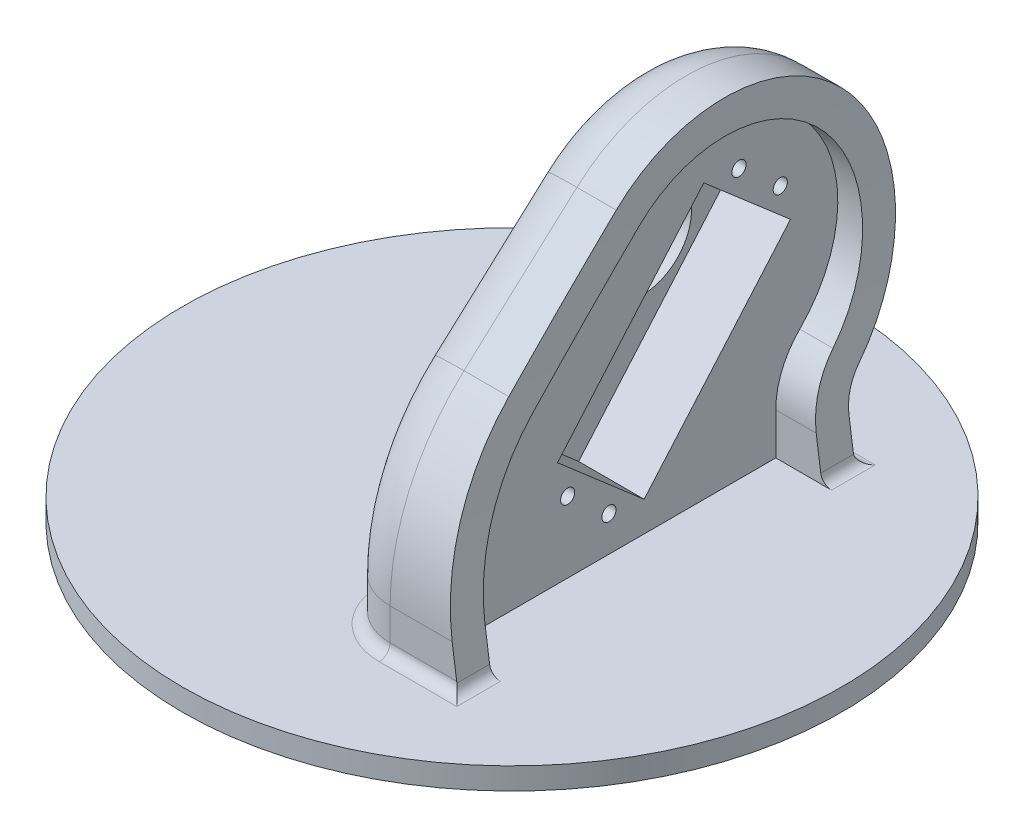
SolidWorks part; units mm, degrees
ref_plane "Front Plane" through (0, 0, 0) normal (0, 0, 1) x (1, 0, 0)
ref_plane "Top Plane" through (0, 0, 0) normal (0, 1, 0) x (1, 0, 0)
ref_plane "Right Plane" through (0, 0, 0) normal (1, 0, 0) x (0, 0, -1)
sketch "Sketch1" plane through (0, 0, 0) normal (0, 1, 0) x (1, 0, 0)
  circle A0 centre (0, 0) radius 60.3947
  dimension "D1" = 120.7894
extrude "Boss-Extrude1" add sketch "Sketch1" along normal blind 1
sketch "Sketch3" plane through (0, 0, 0) normal (1, 0, 0) x (0, 0, -1)
  line L0 (-30.34, 1) -> (30.34, 1)
  line L1 (60.3947, 1) -> (-60.3947, 1) construction
  line L2 (30.34, 1) -> (30.34, 8.64)
  line L3 (-30.34, 1) -> (-30.34, 8.86)
  line L4 (1.924, 53.717) -> (-18.7678, 34.9648)
  arc A0 (30.34, 8.64) -> (34.7349, 19.2481) centre (45.34, 8.64) cw
  arc A1 (34.7349, 19.2481) -> (1.924, 53.717) centre (17.9072, 36.0806) ccw
  arc A2 (-30.34, 8.86) -> (-18.7678, 34.9648) centre (4.89, 8.86) cw
  circle A3 centre (17.9072, 36.0806) radius 9
  point P5 (0, 1)
  point P11 (0, 0)
  point P14 (0, 0)
  dimension "D3" = 15
  dimension "D5" = 35.23
  dimension "D6" = 18
  dimension "D1" = 60.68
  dimension "D2" = 7.64
  dimension "D4" = 7.86
  dimension "D7" = 40.28
extrude "Boss-Extrude3" add sketch "Sketch3" along normal blind 14 from offset 4
sketch "Sketch4" plane through (0, 0, 0) normal (1, 0, 0) x (0, 0, -1)
  line L0 (17.1497, 51.2561) -> (33.0333, 37.5189)
  line L1 (17.1497, 51.2561) -> (-9.6705, 20.2452)
  line L2 (33.0333, 37.5189) -> (6.2131, 6.508)
  line L3 (-9.6705, 20.2452) -> (6.2131, 6.508)
  line L4 (60.3947, 1) -> (-60.3947, 1) construction
  line L5 (3.7396, 35.7507) -> (19.6232, 22.0135) construction
  line L6 (19.6232, 22.0135) -> (3.7396, 35.7507) construction
  line L7 (3.7396, 35.7507) -> (3.5328, 35.6133) construction
  line L8 (11.6814, 28.8821) -> (27.3811, 47.0348) construction
  line L9 (27.3811, 47.0348) -> (11.6814, 28.8821) construction
  line L10 (23.5993, 50.3055) -> (31.1629, 43.764) construction
  circle A0 centre (17.9072, 36.0806) radius 9 construction
  circle A1 centre (23.5993, 50.3055) radius 1.3
  circle A2 centre (31.1629, 43.764) radius 1.3
  circle A3 centre (-0.2364, 7.4586) radius 1.3
  circle A4 centre (-7.8, 14.0001) radius 1.3
  point P16 (27.3811, 47.0348)
  dimension "D7" = 2.6
  dimension "D8" = 2.6
  dimension "D1" = 41
  dimension "D2" = 21
  dimension "D3" = 10.5
  dimension "D4" = 49.145
  dimension "D5" = 10
  dimension "D6" = 3.5
extrude "Cut-Extrude1" cut sketch "Sketch4" along normal through all from offset 6
sketch "Sketch8" plane through (18, 0, 0) normal (1, 0, 0) x (0, 0, -1)
  line L0 (-30.34, 1) -> (30.34, 1) construction
  line L1 (-30.34, 1) -> (30.34, 1)
  line L15 (-33.34, 8.86) -> (-33.34, 1)
  line L16 (33.34, 1) -> (33.34, 8.64)
  line L17 (-0.0906, 55.94) -> (-20.7824, 37.1878)
  line L18 (-33.34, 8.86) -> (-33.34, 1) construction
  line L19 (33.34, 1) -> (33.34, 8.64) construction
  line L20 (-0.0906, 55.94) -> (-20.7824, 37.1878) construction
  line L31 (36.34, 1) -> (36.34, 8.64)
  line L32 (-2.1051, 58.1629) -> (-22.797, 39.4107)
  line L33 (-36.34, 8.86) -> (-36.34, 1)
  line L34 (33.34, 1) -> (33.34, 8.64)
  line L35 (-0.0906, 55.94) -> (-20.7824, 37.1878)
  line L36 (-33.34, 8.86) -> (-33.34, 1)
  line L37 (33.34, 1) -> (33.34, 8.64) construction
  line L38 (-0.0906, 55.94) -> (-20.7824, 37.1878) construction
  line L39 (-33.34, 8.86) -> (-33.34, 1) construction
  line L40 (-36.34, 1) -> (-27.34, 1)
  line L41 (30.34, 1) -> (36.34, 1)
  arc A14 (-20.7824, 37.1878) -> (-33.34, 8.86) centre (4.89, 8.86) ccw
  arc A15 (36.8559, 17.1265) -> (33.34, 8.64) centre (45.34, 8.64) ccw
  arc A16 (36.8559, 17.1265) -> (-0.0906, 55.94) centre (17.9072, 36.0806) ccw
  arc A17 (-20.7824, 37.1878) -> (-33.34, 8.86) centre (4.89, 8.86) ccw construction
  arc A18 (36.8559, 17.1265) -> (33.34, 8.64) centre (45.34, 8.64) ccw construction
  arc A19 (36.8559, 17.1265) -> (-0.0906, 55.94) centre (17.9072, 36.0806) ccw construction
  arc A28 (38.9769, 15.0049) -> (36.34, 8.64) centre (45.34, 8.64) ccw
  arc A29 (38.9769, 15.0049) -> (-2.1051, 58.1629) centre (17.9072, 36.0806) ccw
  arc A30 (-22.797, 39.4107) -> (-36.34, 8.86) centre (4.89, 8.86) ccw
  arc A31 (36.8559, 17.1265) -> (33.34, 8.64) centre (45.34, 8.64) ccw
  arc A32 (36.8559, 17.1265) -> (-0.0906, 55.94) centre (17.9072, 36.0806) ccw
  arc A33 (-20.7824, 37.1878) -> (-33.34, 8.86) centre (4.89, 8.86) ccw
  arc A34 (36.8559, 17.1265) -> (33.34, 8.64) centre (45.34, 8.64) ccw construction
  arc A35 (36.8559, 17.1265) -> (-0.0906, 55.94) centre (17.9072, 36.0806) ccw construction
  arc A36 (-20.7824, 37.1878) -> (-33.34, 8.86) centre (4.89, 8.86) ccw construction
  arc A37 (1.924, 53.717) -> (-27.34, 1) centre (70.6562, -18.9182) ccw
  line M1 (30.34, 1) -> (30.34, 8.64)
  arc M2 (30.34, 8.64) -> (34.7349, 19.2481) centre (45.34, 8.64) cw
  arc M3 (34.7349, 19.2481) -> (1.924, 53.717) centre (17.9072, 36.0806) ccw
  line M4 (1.924, 53.717) -> (-18.7678, 34.9648)
  arc M5 (-18.7678, 34.9648) -> (-30.34, 8.86) centre (4.89, 8.86) ccw
  line M6 (-30.34, 8.86) -> (-30.34, 1)
  dimension "D5" = 100
  dimension "D4" = 3
  dimension "D1" = 3
  dimension "D2" = 3
  dimension "D3" = 3
extrude "Boss-Extrude4" add sketch "Sketch8" along normal blind 9 and the other way up to surface (14 mm away) contours L32 A30 L33 L40 L41 L31 A28 A29 M6 M5 M4 M3 M2 M1 region at (18, 1.996, 31.84) region at (18, 2.0618, 34.84) other way up to face at (4, 20.7286, -4.4128)
sketch "Sketch10" plane through (0, 0, 0) normal (0, 0, 1) x (1, 0, 0)
  line L0 (27, 65.882) -> (21, 65.882)
  line L1 (27, 65.882) -> (4, 65.882) construction
  line L2 (4, 1) -> (27, 1) construction
  line L3 (27, 65.882) -> (27, 1)
  line L4 (27, 1) -> (26.5, 1)
  arc A0 (21, 65.882) -> (26.5, 1) centre (520.9059, 75.5845) ccw
  dimension "D3" = 500
  dimension "D1" = 6
  dimension "D2" = 0.5
extrude "Cut-Extrude2" cut sketch "Sketch10" against normal through all both and the other way through all
fillet "Fillet1" radius 10 6 edges at (4, 4.82, -36.34) (4, 12.0847, -37.0253) (4, 4.93, 36.34) (4, 25.569, 32.8025) (4, 48.7868, 12.451) (4, 56.6278, -39.4927)
fillet "Fillet3" radius 2 7 edges at (26.5, 1, -33.34) (26.5, 1, 33.34) (20.25, 1, -36.34) (6.9289, 1, -33.4111) (4, 1, 0) (6.9289, 1, 33.4111) (20.25, 1, 36.34)
sketch "Sketch11" plane through (0, 0, 0) normal (0, -1, 0) x (1, 0, 0)
  circle A0 centre (0, 0) radius 60.3947
  circle A1 centre (0, 0) radius 56.5
  circle A2 centre (0, 0) radius 46.5
  dimension "D1" = 113
  dimension "D2" = 93
extrude "Boss-Extrude9" add sketch "Sketch11" along normal blind 3 contours A0 A1 region at (-58.6865, 0, 0)
sketch "Sketch14" plane through (0, 0, 0) normal (0, -1, 0) x (-1, 0, 0)
  line L1 (7.5, 15) -> (-7.5, 15)
  line L2 (7.5, 15) -> (7.5, -15)
  line L3 (7.5, -15) -> (-7.5, -15)
  line L4 (-7.5, 15) -> (-7.5, -15)
  line L5 (7.5, 15) -> (-7.5, -15) construction
  line L6 (7.5, -15) -> (-7.5, 15) construction
  circle A0 centre (0, 0) radius 46.5
  dimension "D1" = 93
  dimension "D2" = 30
  dimension "D3" = 15
extrude "Boss-Extrude12" add sketch "Sketch14" along normal blind 3
sketch "Sketch16" plane through (0, 0, 0) normal (0, -1, 0) x (-1, 0, 0)
  line L1 (5.0327, -15) -> (5.0327, 15)
  line L2 (-7.5, -15) -> (7.5, -15) construction
  line L3 (7.5, 15) -> (-7.5, 15) construction
  line L4 (5.0327, 15) -> (5.0327, -15)
  circle A0 centre (5.0327, 10) radius 2
  circle A1 centre (5.0327, -10) radius 2
  dimension "D1" = 4
  dimension "D2" = 4
  dimension "D3" = 5
  dimension "D4" = 5
extrude "Cut-Extrude3" cut sketch "Sketch16" against normal blind 4 contours A1 | A0
